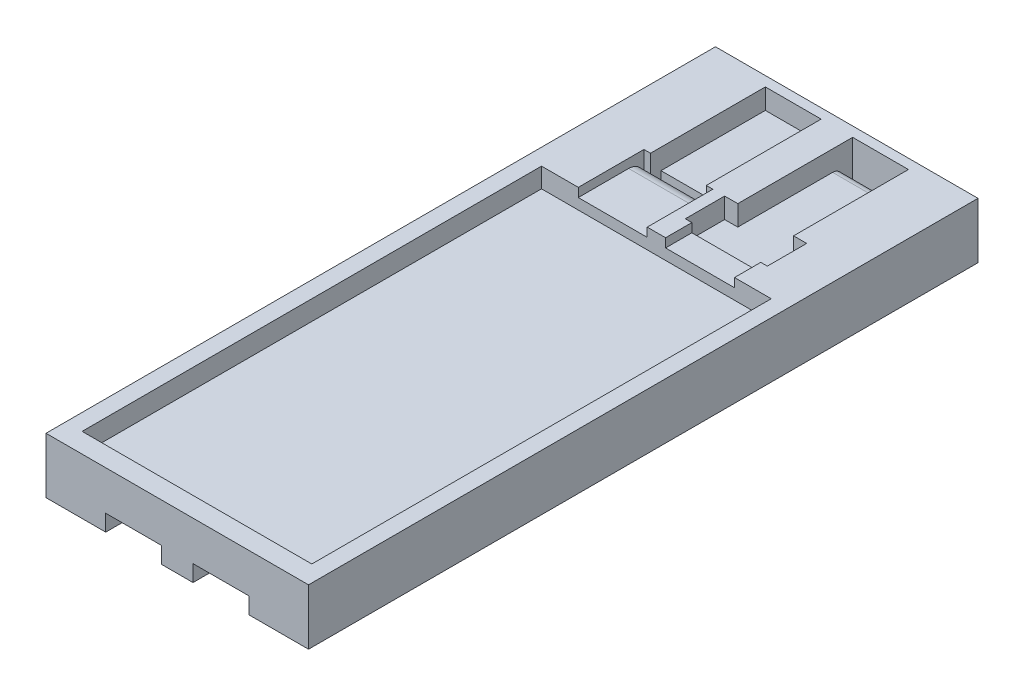
SolidWorks part; units mm, degrees
ref_plane "Front Plane" through (0, 0, 0) normal (0, 0, 1) x (1, 0, 0)
ref_plane "Top Plane" through (0, 0, 0) normal (0, 1, 0) x (1, 0, 0)
ref_plane "Right Plane" through (0, 0, 0) normal (1, 0, 0) x (0, 0, -1)
sketch "Sketch1" plane through (0, 0, 0) normal (0, 1, 0) x (1, 0, 0)
  line L1 (-20, -40) -> (20, -40)
  line L2 (-20, -40) -> (-20, 62)
  line L3 (-20, 62) -> (20, 62)
  line L4 (20, -40) -> (20, 62)
  dimension "D1" = 40
  dimension "D2" = 102
  dimension "D3" = 40
  dimension "D4" = 20
extrude "Boss-Extrude1" add sketch "Sketch1" along normal blind 8.5
sketch "Sketch2" plane through (0, 8.5, 0) normal (0, 1, 0) x (1, 0, 0)
  line L0 (-20, -40) -> (20, -40) construction
  line L1 (-17.5, -37) -> (17.5, -37)
  line L2 (-17.5, -37) -> (-17.5, 33)
  line L3 (-17.5, 33) -> (17.5, 33)
  line L4 (17.5, -37) -> (17.5, 33)
  line L5 (20, -40) -> (20, 62) construction
  line L6 (-20, 62) -> (-20, -40) construction
  dimension "D1" = 3
  dimension "D2" = 35
  dimension "D3" = 2.5
  dimension "D4" = 2.5
  dimension "D5" = 70
extrude "Cut-Extrude1" cut sketch "Sketch2" against normal blind 3
sketch "Sketch3" plane through (0, 8.5, 0) normal (0, 1, 0) x (1, 0, 0)
  line L0 (17.5, 33) -> (-17.5, 33) construction
  line L1 (-11.9, 33) -> (-1.4, 33)
  line L2 (-11.9, 33) -> (-11.9, 43)
  line L3 (-11.9, 43) -> (-1.4, 43)
  line L4 (-1.4, 33) -> (-1.4, 43)
  line L5 (0, 0) -> (0, 15.5865) construction
  line L6 (1.4, 33) -> (1.4, 43)
  line L7 (11.9, 43) -> (1.4, 43)
  line L8 (11.9, 33) -> (11.9, 43)
  line L9 (11.9, 33) -> (1.4, 33)
  dimension "D1" = 10
  dimension "D2" = 10.5
  dimension "D3" = 1.4
extrude "Cut-Extrude2" cut sketch "Sketch3" against normal blind 1.35
sketch "Sketch4" plane through (0, 8.5, 0) normal (0, 1, 0) x (1, 0, 0)
  line L0 (11.9, 43) -> (1.4, 43) construction
  line L1 (0.4, 37) -> (12.9, 37)
  line L2 (0.4, 37) -> (0.4, 43)
  line L3 (0.4, 43) -> (12.9, 43)
  line L4 (12.9, 37) -> (12.9, 43)
  line L5 (1.4, 43) -> (1.4, 33) construction
  dimension "D1" = 6
  dimension "D2" = 12.5
  dimension "D3" = 1
extrude "Cut-Extrude3" cut sketch "Sketch4" against normal blind 3.1
sketch "Sketch5" plane through (0, 8.5, 0) normal (0, 1, 0) x (1, 0, 0)
  line L0 (12.9, 43) -> (0.4, 43) construction
  line L1 (2.4, 43) -> (10.9, 43)
  line L2 (2.4, 43) -> (2.4, 60.5)
  line L3 (2.4, 60.5) -> (10.9, 60.5)
  line L4 (10.9, 43) -> (10.9, 60.5)
  line L5 (12.9, 37) -> (12.9, 43) construction
  dimension "D1" = 17.5
  dimension "D2" = 8.5
  dimension "D3" = 2
extrude "PCB place" cut sketch "Sketch5" against normal up to surface (3.1 mm away) up to face at (6.65, 5.4, -40)
sketch "Sketch6" plane through (0, 5.4, 0) normal (0, 1, 0) x (1, 0, 0)
  line L0 (10.9, 43) -> (10.9, 60.5) construction
  line L1 (2.4, 60.5) -> (10.9, 60.5)
  line L2 (2.4, 60.5) -> (2.4, 58.9)
  line L3 (2.4, 58.9) -> (10.9, 58.9)
  line L4 (10.9, 60.5) -> (10.9, 58.9)
  dimension "D1" = 1.6
extrude "Nickel strip hole" cut sketch "Sketch6" against normal through all
sketch "Sketch7" plane through (0, 8.5, 0) normal (0, 1, 0) x (1, 0, 0)
  line L0 (10.9, 60.5) -> (2.4, 60.5) construction
  line L1 (-2.4, 43) -> (-10.9, 43)
  line L2 (-2.4, 43) -> (-2.4, 60.5)
  line L3 (-2.4, 60.5) -> (-10.9, 60.5)
  line L4 (-10.9, 43) -> (-10.9, 60.5)
  line L5 (-11.9, 43) -> (-11.9, 33) construction
  line L6 (-1.4, 43) -> (-11.9, 43) construction
  dimension "D1" = 8.5
  dimension "D2" = 1
extrude "Cut-Extrude4" cut sketch "Sketch7" against normal up to surface (3.1 mm away) up to face at (6.65, 5.4, -45.475)
sketch "Sketch8" plane through (0, 5.4, 0) normal (0, 1, 0) x (1, 0, 0)
  line L0 (-10.9, 60.5) -> (-10.9, 43) construction
  line L1 (-2.4, 43) -> (-10.9, 43)
  line L2 (-2.4, 43) -> (-2.4, 44.6)
  line L3 (-2.4, 44.6) -> (-10.9, 44.6)
  line L4 (-10.9, 43) -> (-10.9, 44.6)
  dimension "D1" = 1.6
extrude "Cut-Extrude5" cut sketch "Sketch8" against normal blind 10
sketch "Sketch9" plane through (0, 0, 0) normal (0, -1, 0) x (1, 0, 0)
  line L0 (20, -62) -> (-20, -62) construction
  line L1 (-2.4, -62) -> (-10.9, -62)
  line L2 (-2.4, -62) -> (-2.4, 40)
  line L3 (-2.4, 40) -> (-10.9, 40)
  line L4 (-10.9, -62) -> (-10.9, 40)
  line L5 (2.4, -62) -> (10.9, -62)
  line L6 (2.4, -62) -> (2.4, 40)
  line L7 (2.4, 40) -> (10.9, 40)
  line L8 (10.9, -62) -> (10.9, 40)
  line L9 (-10.9, -43) -> (-10.9, -44.6) construction
  line L10 (-2.4, -44.6) -> (-2.4, -43) construction
  line L11 (-20, 40) -> (20, 40) construction
  line L12 (2.4, -60.5) -> (2.4, -58.9) construction
  line L13 (10.9, -58.9) -> (10.9, -60.5) construction
extrude "Nickel strip rail" cut sketch "Sketch9" against normal blind 2.5
fillet "Fillet3" 2 edges at (-6.65, 7.15, -43) (-6.65, 2.5, -43) type full round first side face at (-6.65, 7.15, -39.6667) second side face at (-6.65, 2.5, -1.5) middle face at (-6.65, 4.825, -43)
fillet "Fillet4" 2 edges at (6.65, 5.4, -58.9) (6.65, 2.5, -58.9) type full round first side face at (6.65, 5.4, -45.475) second side face at (6.65, 2.5, -9.45) middle face at (6.65, 3.95, -58.9)
